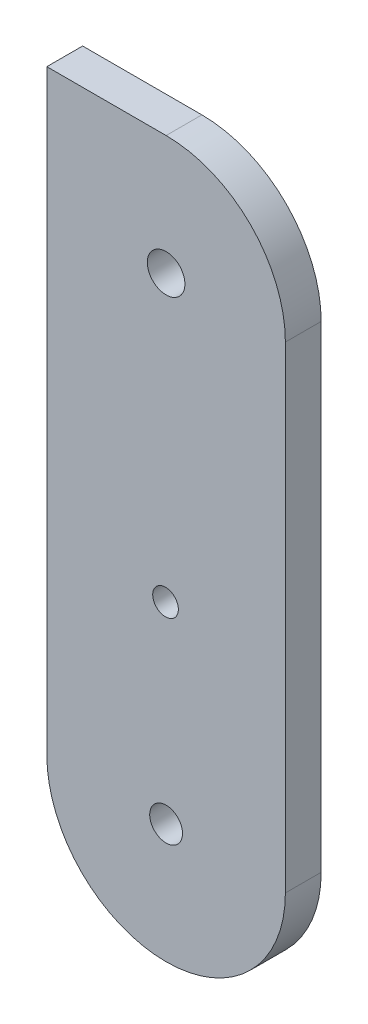
SolidWorks part; units mm, degrees
ref_plane "Front Plane" through (0, 0, 0) normal (0, 0, 1) x (1, 0, 0)
ref_plane "Top Plane" through (0, 0, 0) normal (0, 1, 0) x (1, 0, 0)
ref_plane "Right Plane" through (0, 0, 0) normal (1, 0, 0) x (0, 0, -1)
sketch "Sketch1" plane through (0, 0, 0) normal (0, 0, 1) x (1, 0, 0)
  line L0 (-16.25, 39.1835) -> (-16.25, 89.1835) construction
  line L1 (-26.25, 79.1835) -> (-26.25, 39.1835)
  line L2 (-6.25, 79.1835) -> (-6.25, 39.1835)
  line L3 (-16.25, 39.1835) -> (-16.25, 58.1835) construction
  line L4 (-18.5364, 55.9338) -> (-20.25, 39.1835)
  line L5 (-14.0364, 55.9338) -> (-12.25, 39.1835)
  line L6 (-19.5359, 55.9895) -> (-21.2497, 39.2373)
  line L7 (-13.0369, 55.9918) -> (-11.2503, 39.2396)
  line L10 (-26.25, 69.1835) -> (-26.25, 89.1835)
  line L11 (-26.25, 89.1835) -> (-6.25, 89.1835)
  line L12 (-6.25, 69.1835) -> (-6.25, 89.1835)
  line L13 (-26.25, 69.1835) -> (-6.25, 89.1835) construction
  line L14 (-26.25, 89.1835) -> (-6.25, 69.1835) construction
  arc A0 (-26.25, 39.1835) -> (-6.25, 39.1835) centre (-16.25, 39.1835) ccw
  arc A1 (-6.25, 79.1835) -> (-16.25, 89.1835) centre (-16.25, 79.1835) ccw
  arc A2 (-20.25, 39.1835) -> (-12.25, 39.1835) centre (-16.25, 39.1835) ccw
  arc A3 (-14.0364, 55.9338) -> (-18.5364, 55.9338) centre (-16.2864, 55.9338) ccw
  arc A4 (-13.0369, 55.9918) -> (-19.5359, 55.9895) centre (-16.2864, 55.9338) ccw
  arc A5 (-21.2497, 39.2373) -> (-11.2503, 39.2396) centre (-16.25, 39.1835) ccw
  circle A6 centre (-16.2988, 55.2834) radius 1.075
  circle A7 centre (-16.25, 39.1835) radius 1.375
  dimension "D1" = 20
  dimension "D3" = 20
  dimension "D4" = 8
  dimension "D6" = 4.5
  dimension "D8" = 2.15
  dimension "D9" = 2.75
  dimension "D2" = 50
  dimension "D5" = 19
  dimension "D7" = 1
extrude "Boss-Extrude1" add sketch "Sketch1" along normal blind 3 contours L2 A1 L1 A0 A5 L6 A4 L7 | L6 A5 L7 A4 A3 L5 A2 L4 | L5 A3 L4 A2 A7 A6 region at (-16.424, 62.5679, 0) region at (-16.2643, 45.6937, 0) region at (-16.2874, 58.9145, 0)
extrude "Boss-Extrude2" add sketch "Sketch1<4>" against normal blind 4 contours L6 A5 L7 A4 A3 L5 A2 L4 region at (-16.2874, 58.9145, 0)
sketch "Sketch1<4>" plane through (0, 0, 0) normal (0, 0, 1) x (1, 0, 0) same geometry as "Sketch1"
sketch "Sketch3" plane through (0, 0, 3) normal (0, 0, 1) x (1, 0, 0)
  circle A0 centre (-16.25, 79.1835) radius 1.575
  dimension "D1" = 3.15
extrude "Cut-Extrude1" cut sketch "Sketch3" against normal blind 10 contours A0 region at (-16.25, 79.1835, 3)
